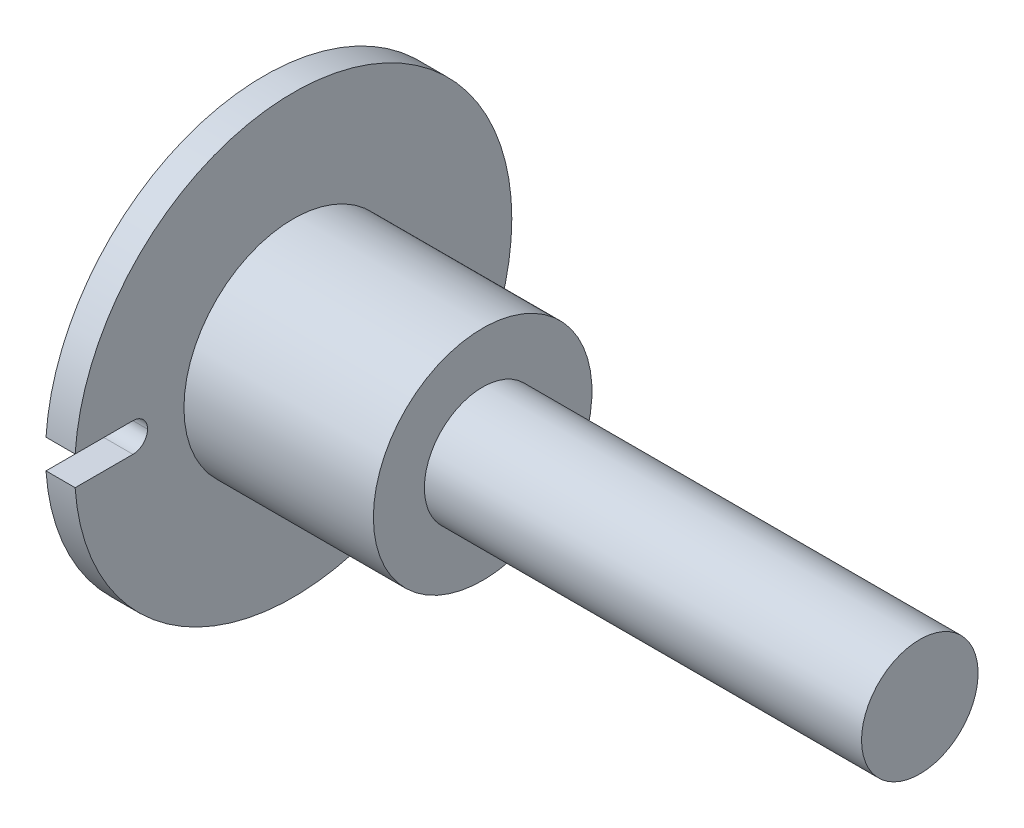
SolidWorks part; units mm, degrees
ref_plane "Ebene vorne" through (0, 0, 0) normal (0, 0, 1) x (1, 0, 0)
ref_plane "Ebene oben" through (0, 0, 0) normal (0, 1, 0) x (1, 0, 0)
ref_plane "Ebene rechts" through (0, 0, 0) normal (1, 0, 0) x (0, 0, -1)
sketch "Skizze1" plane through (0, 0, 0) normal (0, 0, 1) x (1, 0, 0)
  line L0 (0, 0) -> (62.9468, 0) construction
  line L1 (0, 3.2) -> (10, 3.2)
  line L2 (10, 3.2) -> (11.9228, 0)
  line L3 (0, 3.2) -> (0, 7.5)
  line L4 (2, 7.5) -> (15, 7.5)
  line L5 (15, 7.5) -> (15, 4)
  line L6 (15, 4) -> (45, 4)
  line L7 (45, 4) -> (45, 0)
  line L8 (45, 0) -> (11.9228, 0)
  line L11 (0, 7.5) -> (0, 15)
  line L12 (0, 15) -> (2, 15)
  line L13 (2, 7.5) -> (2, 15)
  dimension "D1" = 3.2
  dimension "D2" = 59
  dimension "D3" = 10
  dimension "D4" = 15
  dimension "D5" = 7.5
  dimension "D6" = 4
  dimension "D7" = 30
  dimension "D8" = 2
  dimension "D9" = 15
revolve "Rotation1" add sketch "Skizze1" angle 360 about L0
sketch "Skizze3" plane through (0, 0, 0) normal (0, 1, 0) x (1, 0, 0)
  line L0 (45, 4) -> (15, 4) construction
  line L1 (29, 4) -> (35, 4)
  line L2 (29, 4) -> (29, 3.5)
  line L3 (29, 3.5) -> (35, 3.5)
  line L4 (35, 4) -> (35, 3.5)
  line L6 (45, -4) -> (45, 4) construction
  dimension "D1" = 6
  dimension "D2" = 0.5
  dimension "D3" = 10
extrude "Schnitt-Linear austragen1" cut sketch "Skizze3" against normal through all and the other way through all
ref_plane "Ebene1" through (0, 0, -7.5) normal (0, 0, 1) x (1, 0, 0)
sketch "Skizze7" plane through (0, 0, -7.5) normal (0, 0, 1) x (1, 0, 0)
  line L0 (0, 7.5) -> (0, -7.5) construction
  point P0 (5, 0)
  dimension "D1" = 5
hole_wizard "M4 Gewindebohrung2" positions "Skizze9" profile "Skizze8" tap size "M4" standard "DIN"
sketch "Skizze9" plane through (0, 0, -7.5) normal (0, 0, 1) x (1, 0, 0)
  point P0 (5, 0)
sketch "Skizze8" plane through (5, 0, -7.5) normal (1, 0, 0) x (0, 1, 0)
  line L0 (0, 0) -> (0, 9.4914)
  line L1 (0, 9.4914) -> (1.65, 8.5)
  line L2 (1.65, 8.5) -> (1.65, 0)
  line L5 (1.65, 0) -> (0, 0)
  line L10 (0, 9.4914) -> (-1.65, 8.5) construction
  line L11 (0, -6.35) -> (0, 107.95) construction
  dimension "Bohrerdurchmesser" = 3.3
  dimension "Bohrungstiefe" = 8.5
  dimension "Spitzenwinkel" = 118
cosmetic thread "Bohrungsgewinde1" parameters "D1"=4.7582, "D2"=4
sketch "Skizze10" plane through (0, 0, 0) normal (-1, 0, 0) x (0, 0, 1)
  line L1 (15.8388, 1) -> (10, 1)
  line L2 (15.8388, 1) -> (15.8388, -1)
  line L3 (15.8388, -1) -> (10, -1)
  line L4 (10, 1) -> (10, -1)
  dimension "D1" = 2
  dimension "D2" = 1
  dimension "D3" = 10
extrude "Schnitt-Linear austragen2" cut sketch "Skizze10" against normal blind 2
fillet "Verrundung1" radius 1 2 edges at (1, -1, 10) (1, 1, 10)
